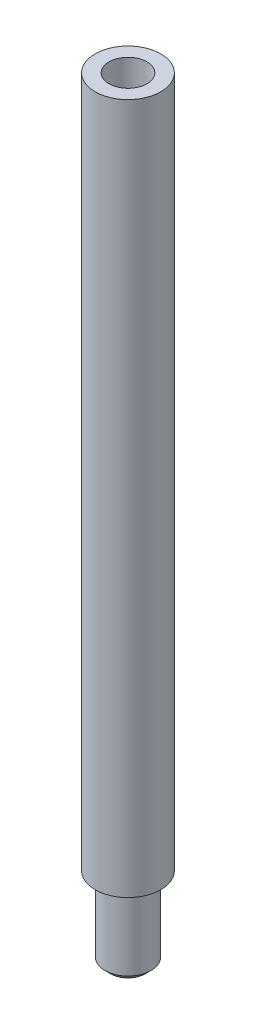
SolidWorks part; units mm, degrees
ref_plane "Front Plane" through (0, 0, 0) normal (0, 0, 1) x (1, 0, 0)
ref_plane "Top Plane" through (0, 0, 0) normal (0, 1, 0) x (1, 0, 0)
ref_plane "Right Plane" through (0, 0, 0) normal (1, 0, 0) x (0, 0, -1)
sketch "Sketch1" plane through (0, 0, 0) normal (0, 1, 0) x (1, 0, 0)
  circle A0 centre (0, 0) radius 2.85
  circle A1 centre (0, 0) radius 2
extrude "Boss-Extrude1" add sketch "Sketch1" along normal blind 60 contours A1 | A0 A1 region at (-2.7694, 0, 0) region at (0, 0, 0)
extrude "Boss-Extrude2" add sketch "Sketch1<4>" against normal blind 7 contours A1 region at (0, 0, 0)
sketch "Sketch1<4>" plane through (0, 0, 0) normal (0, 1, 0) x (1, 0, 0) same geometry as "Sketch1"
hole_wizard "M4x0.7 Tapped Hole1" positions "Sketch2" profile "Sketch3" tap size "M4x0.7" standard "ANSI Metric"
sketch "Sketch2" plane through (0, 60, 0) normal (0, 1, 0) x (1, 0, 0)
  point P0 (0, 0)
cosmetic thread "Hole Thread1" parameters "D2"=4
sketch "Sketch3" plane through (0, 60, 0) normal (1, 0, 0) x (0, 0, 1)
  line L0 (0, 0) -> (0, 11.0914)
  line L1 (0, 11.0914) -> (1.65, 10.1)
  line L2 (1.65, 10.1) -> (1.65, 0)
  line L5 (1.65, 0) -> (0, 0)
  line L10 (0, 11.0914) -> (-1.65, 10.1) construction
  line L11 (0, -6.35) -> (0, 107.95) construction
  dimension "Tap Drill Dia." = 3.3
  dimension "Tap Drill Depth" = 10.1
  dimension "Drill Angle" = 118
chamfer "Chamfer1" distance 0.5 angle 45 1 edges at (0, -7, 2)
